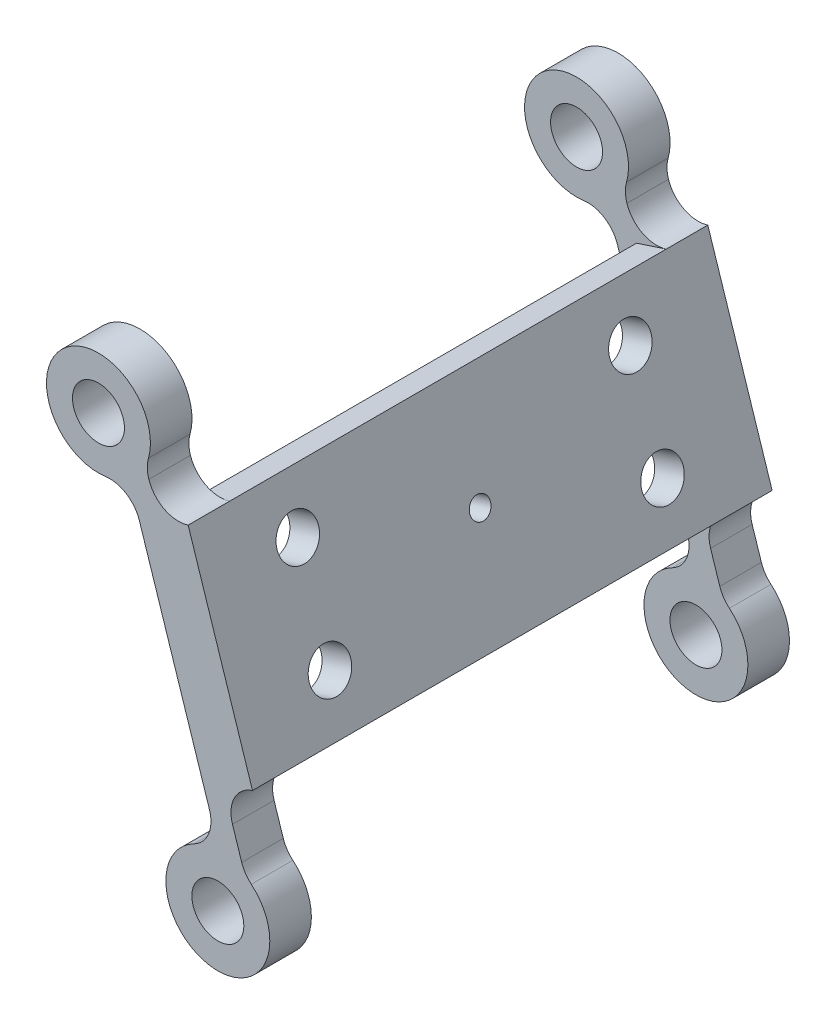
SolidWorks part; units mm, degrees
ref_plane "Front Plane" through (0, 0, 0) normal (0, 0, 1) x (1, 0, 0)
ref_plane "Top Plane" through (0, 0, 0) normal (0, 1, 0) x (1, 0, 0)
ref_plane "Right Plane" through (0, 0, 0) normal (1, 0, 0) x (0, 0, -1)
sketch "Sketch1" plane through (0, 0, 0) normal (0, 0, 1) x (1, 0, 0)
  line L2 (-17.3976, 40.0711) -> (-7.8424, 10.7162)
  line L3 (-10.6381, 12.6112) -> (-10.2569, 11.44)
  line L4 (-18.7542, 37.5449) -> (-10.6381, 12.6112)
  line L5 (-18.7542, 37.5449) -> (-18.9568, 38.1671)
  circle A0 centre (-21.9266, 42.1896) radius 2.5
  arc A2 (-17.3976, 40.0711) -> (-18.9568, 38.1671) centre (-21.9266, 42.1896) ccw
  arc A3 (-10.2569, 11.44) -> (-7.8424, 10.7162) centre (-10.4388, 6.4433) ccw
  circle A5 centre (-10.4388, 6.4433) radius 2.5
extrude "Boss-Extrude1" add sketch "Sketch1" along normal blind 4 contours L2 L4 A0 A5 region at (-13.1006, 25.2372, 0)
sketch "Sketch2" plane through (0, 0, 4) normal (0, 0, 1) x (1, 0, 0)
  line L0 (-16.1484, 36.2334) -> (-9.958, 17.2156)
  line L1 (-16.1484, 36.2334) -> (-13.2958, 37.162)
  line L2 (-9.958, 17.2156) -> (-7.1053, 18.1442)
  line L3 (-13.2958, 37.162) -> (-7.1053, 18.1442)
  line L4 (-17.3976, 40.0711) -> (-7.8424, 10.7162) construction
  dimension "D1" = 3
  dimension "D2" = 20
extrude "Boss-Extrude2" add sketch "Sketch2" against normal blind 50
ref_plane "Plane1" through (0, 0, -21) normal (0, 0, 1) x (1, 0, 0)
mirror "Mirror1" about plane through (0, 0, -21) normal (0, 0, 1) of "Boss-Extrude1"
sketch "Sketch3" plane through (-3.937, -1.2815, 0) normal (-0.9509, -0.3095, 0) x (0, 0, 1)
  line L0 (0, 39.4524) -> (0, 34.4524) construction
  line L1 (0, 34.4524) -> (-5, 34.4524) construction
  line L2 (0, 29.4524) -> (-10.938, 29.4524) construction
  line L3 (0, 39.4524) -> (0, 19.4524) construction
  line L4 (-21, 19.4524) -> (-21, 39.4524) construction
  line L7 (-42, 19.4524) -> (0, 19.4524) construction
  line L8 (-42, 39.4524) -> (0, 39.4524) construction
  circle A0 centre (-5, 34.4524) radius 2
  circle A1 centre (-5, 24.4524) radius 2
  circle A2 centre (-37, 24.4524) radius 2
  circle A3 centre (-37, 34.4524) radius 2
  circle A4 centre (-21, 29.4524) radius 1
extrude "Cut-Extrude1" cut sketch "Sketch3" against normal blind 10
fillet "Fillet1" radius 3 12 edges at (-9.958, 17.2156, 2) (-9.958, 17.2156, -44) (-16.1484, 36.2334, -44) (-16.1484, 36.2334, 2) (-10.2569, 11.44, 2) (-7.8424, 10.7162, 2) (-7.8424, 10.7162, -44) (-10.2569, 11.44, -44) (-18.9568, 38.1671, -44) (-17.3976, 40.0711, -44) (-17.3976, 40.0711, 2) (-18.9568, 38.1671, 2)
ref_plane "Plane2" through (0, 0, -21) normal (0, 0, -1) x (-1, 0, 0)
ref_plane "Plane3" through (-9.1162, 28.006, 0) normal (0.3095, -0.9509, 0) x (-0.9509, -0.3095, 0)
sketch "Sketch4" plane through (-9.1162, 28.006, 0) normal (0.3095, -0.9509, 0) x (-0.9509, -0.3095, 0)
  line L0 (1.1403, 23.5892) -> (1.1403, 30.713)
  line L1 (1.1403, 42) -> (1.1403, 0) construction
  arc A0 (-0.6494, 29.5072) -> (-0.6494, 25.5072) centre (-0.6494, 27.5072) ccw
  circle A1 centre (-0.6494, 27.5072) radius 1.5
  spline S0 degree 2 poles (-0.6494, 29.5072) (0.4743, 29.7786) (1.1403, 30.713) knots 0 0 0 1 1 1
  spline S1 degree 2 poles (-0.6494, 25.5072) (0.7375, 25.0283) (1.1403, 23.5892) knots 0 0 0 1 1 1
  dimension "D1" = 4
  dimension "D2" = 3
sketch "Sketch5" plane through (-9.1162, 28.006, 0) normal (0.3095, -0.9509, 0) x (-0.9509, -0.3095, 0)
  line L0 (4.1403, 30.713) -> (4.1403, 23.5892)
  line L1 (4.1403, 42) -> (4.1403, 0) construction
  circle A0 centre (5.8855, 27.4852) radius 1.5
  arc A1 (5.8855, 25.4852) -> (5.8855, 29.4852) centre (5.8855, 27.4852) ccw
  spline S0 degree 2 poles (5.8855, 29.4852) (4.5339, 29.8504) (4.1403, 30.713) knots 0 0 0 0.549004 0.549004 0.549004
  spline S1 degree 2 poles (5.8855, 25.4852) (4.261, 24.6246) (4.1403, 23.5892) knots 0 0 0 0.499768 0.499768 0.499768
  dimension "D1" = 3
  dimension "D2" = 4
extrude "Boss-Extrude4" add sketch "Sketch5" along normal mid plane 5
